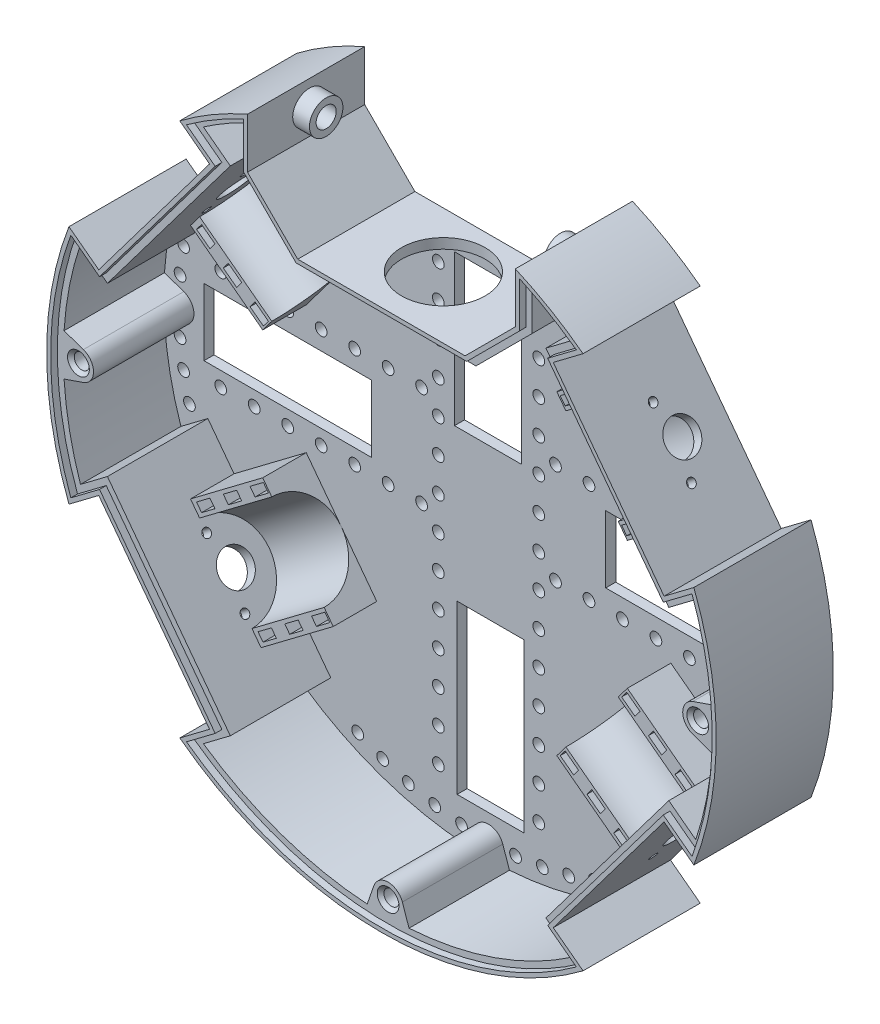
SolidWorks part; units mm, degrees
ref_plane "Front Plane" through (0, 0, 0) normal (0, 0, 1) x (1, 0, 0)
ref_plane "Top Plane" through (0, 0, 0) normal (0, 1, 0) x (1, 0, 0)
ref_plane "Right Plane" through (0, 0, 0) normal (1, 0, 0) x (0, 0, -1)
sketch "Sketch1" plane through (0, 0, 0) normal (0, 0, 1) x (1, 0, 0)
  circle A0 centre (0, 0) radius 100
  dimension "D1" = 200
extrude "Boss-Extrude1" add sketch "Sketch1" along normal blind 3
sketch "Sketch2" plane through (0, 0, 3) normal (0, 0, 1) x (1, 0, 0)
  line L0 (-40, 91.6515) -> (-40, 76.6515)
  line L1 (-40, 76.6515) -> (-25, 61.6515)
  line L2 (-25, 61.6515) -> (25, 61.6515)
  line L3 (25, 61.6515) -> (40, 76.6515)
  line L4 (40, 76.6515) -> (40, 91.6515)
  line L5 (-40, 91.6515) -> (40, 91.6515) construction
  line L6 (-40, 76.6515) -> (40, 76.6515) construction
  circle A0 centre (0, 0) radius 100 construction
  arc A1 (-40, 91.6515) -> (40, 91.6515) centre (0, 0) cw
  dimension "D1" = 80
  dimension "D2" = 15
  dimension "D3" = 15
  dimension "D4" = 15
extrude "Cut-Extrude1" cut sketch "Sketch2" against normal blind 3
sketch "Sketch3" plane through (0, 0, 3) normal (0, 0, 1) x (1, 0, 0)
  line L0 (0, 0) -> (67.884, 51.1543) construction
  line L1 (0, 0) -> (100, 0) construction
  line L2 (51.3341, 73.1168) -> (84.4339, 29.1918)
  line L3 (51.3341, 73.1168) -> (75.2932, 91.1712)
  line L4 (84.4339, 29.1918) -> (108.393, 47.2463)
  line L5 (75.2932, 91.1712) -> (108.393, 47.2463)
  arc A1 (-40, 91.6515) -> (40, 91.6515) centre (0, 0) ccw construction
  dimension "D1" = 37
  dimension "D2" = 55
  dimension "D3" = 30
  dimension "D4" = 85
extrude "Cut-Extrude2" cut sketch "Sketch3" against normal blind 3
sketch "Sketch4" plane through (0, 0, 3) normal (0, 0, 1) x (1, 0, 0)
  line L0 (57.3523, 65.1304) -> (78.4158, 37.1782)
  line L1 (57.3523, 65.1304) -> (33.3932, 47.0759)
  line L2 (78.4158, 37.1782) -> (54.4567, 19.1237)
  line L3 (33.3932, 47.0759) -> (54.4567, 19.1237)
  line L4 (51.3341, 73.1168) -> (84.4339, 29.1918) construction
  point P6 (67.884, 51.1543)
  dimension "D1" = 35
  dimension "D2" = 30
extrude "Boss-Extrude2" add sketch "Sketch4" along normal blind 13
sketch "Sketch5" plane through (67.884, 51.1543, 0) normal (0.7986, 0.6018, 0) x (0, 0, -1)
  line L0 (-16, -17.5) -> (-16, 17.5) construction
  circle A0 centre (-16, 0) radius 13
  dimension "D1" = 26
extrude "Cut-Extrude3" cut sketch "Sketch5" against normal blind 50
sketch "Sketch9" plane through (0, 0, 16) normal (0, 0, 1) x (1, 0, 0)
  line L0 (53.1159, 59.1208) -> (71.4712, 34.7624) construction
  line L1 (75.7076, 40.772) -> (60.0604, 61.5365) construction
  line L2 (67.884, 51.1543) -> (62.2936, 46.9416) construction
  line L3 (68.7224, 34.2561) -> (72.7156, 37.2652)
  line L4 (68.7224, 34.2561) -> (70.2269, 32.2595)
  line L5 (72.7156, 37.2652) -> (74.2201, 35.2686)
  line L6 (70.2269, 32.2595) -> (74.2201, 35.2686)
  line L7 (68.7224, 34.2561) -> (74.2201, 35.2686) construction
  line L8 (72.7156, 37.2652) -> (70.2269, 32.2595) construction
  line L9 (51.7485, 22.7176) -> (75.7076, 40.772) construction
  line L10 (50.3821, 58.5945) -> (54.3753, 61.6035)
  line L11 (50.3821, 58.5945) -> (51.8565, 56.638)
  line L12 (54.3753, 61.6035) -> (55.8496, 59.6471)
  line L13 (51.8565, 56.638) -> (55.8496, 59.6471)
  line L14 (50.3821, 58.5945) -> (55.8496, 59.6471) construction
  line L15 (54.3753, 61.6035) -> (51.8565, 56.638) construction
  line L16 (60.0604, 61.5365) -> (36.1014, 43.4821) construction
  dimension "D1" = 5
  dimension "D2" = 30.5
  dimension "D3" = 7
  dimension "D4" = 2.5
  dimension "D5" = 2.4498
  dimension "D6" = 5
extrude "Cut-Extrude5" cut sketch "Sketch9" against normal through all
pattern_linear "LPattern1" count 3 spacing 10 along (-0.7986, -0.6018, 0) of "Cut-Extrude5"
sketch "Sketch29" plane through (0, 0, 0) normal (0, 0, -1) x (-1, 0, 0)
  line L0 (-72.7156, 37.2652) -> (-68.7224, 34.2561)
  line L1 (-72.7156, 37.2652) -> (-55.8496, 59.6471)
  line L2 (-68.7224, 34.2561) -> (-51.8565, 56.638)
  line L3 (-55.8496, 59.6471) -> (-51.8565, 56.638)
  line L4 (-51.8565, 56.638) -> (-55.8496, 59.6471) construction
  line L17 (-64.7292, 31.2471) -> (-47.8633, 53.6289)
  line L18 (-60.736, 28.238) -> (-43.8701, 50.6198)
  line L19 (-47.8633, 53.6289) -> (-43.8701, 50.6198)
  line L20 (-56.7429, 25.2289) -> (-39.8769, 47.6108)
  line L21 (-52.7497, 22.2198) -> (-35.8838, 44.6017)
  line L22 (-39.8769, 47.6108) -> (-35.8838, 44.6017)
  line M1 (-64.7292, 31.2471) -> (-60.736, 28.238)
  line M11 (-35.8838, 44.6017) -> (-39.8769, 47.6108)
  line M13 (-56.7429, 25.2289) -> (-52.7497, 22.2198)
  line M19 (-43.8701, 50.6198) -> (-47.8633, 53.6289)
  line M25 (-72.7156, 37.2652) -> (-68.7224, 34.2561)
  line M31 (-51.8565, 56.638) -> (-55.8496, 59.6471)
  dimension "D1" = 3
extrude "Cut-Extrude15" cut sketch "Sketch29" against normal blind 2 contours L2 L1 M25 M31 | L18 L17 M1 M19 | L21 L20 M13 M11
mirror "Mirror1" about plane through (0, 0, 0) normal (1, 0, 0) of "Cut-Extrude15", "Cut-Extrude5", "LPattern1", "Cut-Extrude2", "Boss-Extrude2", "Cut-Extrude3" second plane through (0, 0, 0) second plane normal (0, 1, 0)
ref_plane "Plane1" through (-93.3343, -35.8987, 3) normal (-0.7986, -0.6018, 0) x (0, 0, 1)
sketch "Sketch13" plane through (0, 0, 3) normal (0, 0, 1) x (1, 0, 0)
  line L18 (-47.1328, -73.7072) -> (-55.1831, -79.7736)
  line L19 (55.1831, -79.7736) -> (47.1328, -73.7072)
  line L20 (47.1328, -73.7072) -> (83.8435, -24.9904)
  line L21 (83.8435, -24.9904) -> (91.8938, -31.0568)
  line L22 (91.8938, 31.0568) -> (83.8435, 24.9904)
  line L28 (83.8435, 24.9904) -> (47.1328, 73.7072)
  line L31 (47.1328, 73.7072) -> (55.1831, 79.7736)
  line L32 (43, 86.9483) -> (43, 75.4089)
  line L33 (43, 75.4089) -> (26.2426, 58.6515)
  line L51 (26.2426, 58.6515) -> (-26.2426, 58.6515)
  line L52 (-26.2426, 58.6515) -> (-43, 75.4089)
  line L53 (-43, 75.4089) -> (-43, 86.9483)
  line L54 (-55.1831, 79.7736) -> (-47.1328, 73.7072)
  line L55 (-47.1328, 73.7072) -> (-83.8435, 24.9904)
  line L56 (-83.8435, 24.9904) -> (-91.8938, 31.0568)
  line L57 (-91.8938, -31.0568) -> (-83.8435, -24.9904)
  line L58 (-83.8435, -24.9904) -> (-47.1328, -73.7072)
  line L59 (-51.3341, -73.1168) -> (-60.2344, -79.8236)
  line L65 (-84.4339, -29.1918) -> (-51.3341, -73.1168)
  line L68 (-93.3343, -35.8987) -> (-84.4339, -29.1918)
  line L69 (-84.4339, 29.1918) -> (-93.3343, 35.8987)
  line L70 (-51.3341, 73.1168) -> (-84.4339, 29.1918)
  line L71 (-60.2344, 79.8236) -> (-51.3341, 73.1168)
  line L72 (-40, 76.6515) -> (-40, 91.6515)
  line L73 (-25, 61.6515) -> (-40, 76.6515)
  line L74 (25, 61.6515) -> (-25, 61.6515)
  line L75 (40, 76.6515) -> (25, 61.6515)
  line L76 (40, 91.6515) -> (40, 76.6515)
  line L80 (51.3341, 73.1168) -> (60.2344, 79.8236)
  line L86 (84.4339, 29.1918) -> (51.3341, 73.1168)
  line L87 (93.3343, 35.8987) -> (84.4339, 29.1918)
  line L88 (84.4339, -29.1918) -> (93.3343, -35.8987)
  line L89 (51.3341, -73.1168) -> (84.4339, -29.1918)
  line L90 (60.2344, -79.8236) -> (51.3341, -73.1168)
  line L91 (-51.3341, -73.1168) -> (-60.2344, -79.8236)
  line L92 (-84.4339, -29.1918) -> (-51.3341, -73.1168)
  line L93 (-93.3343, -35.8987) -> (-84.4339, -29.1918)
  line L94 (-84.4339, 29.1918) -> (-93.3343, 35.8987)
  line L95 (-51.3341, 73.1168) -> (-84.4339, 29.1918)
  line L96 (-60.2344, 79.8236) -> (-51.3341, 73.1168)
  line L97 (-40, 76.6515) -> (-40, 91.6515)
  line L98 (-25, 61.6515) -> (-40, 76.6515)
  line L99 (25, 61.6515) -> (-25, 61.6515)
  line L100 (40, 76.6515) -> (25, 61.6515)
  line L101 (40, 91.6515) -> (40, 76.6515)
  line L102 (51.3341, 73.1168) -> (60.2344, 79.8236)
  line L103 (84.4339, 29.1918) -> (51.3341, 73.1168)
  line L104 (93.3343, 35.8987) -> (84.4339, 29.1918)
  line L105 (84.4339, -29.1918) -> (93.3343, -35.8987)
  line L106 (51.3341, -73.1168) -> (84.4339, -29.1918)
  line L107 (60.2344, -79.8236) -> (51.3341, -73.1168)
  arc A6 (-55.1831, -79.7736) -> (55.1831, -79.7736) centre (0, 0) ccw
  arc A9 (91.8938, -31.0568) -> (91.8938, 31.0568) centre (0, 0) ccw
  arc A15 (55.1831, 79.7736) -> (43, 86.9483) centre (0, 0) ccw
  arc A16 (-43, 86.9483) -> (-55.1831, 79.7736) centre (0, 0) ccw
  arc A20 (-91.8938, 31.0568) -> (-91.8938, -31.0568) centre (0, 0) ccw
  arc A21 (-60.2344, -79.8236) -> (60.2344, -79.8236) centre (0, 0) ccw
  arc A22 (-93.3343, 35.8987) -> (-93.3343, -35.8987) centre (0, 0) ccw
  arc A26 (-40, 91.6515) -> (-60.2344, 79.8236) centre (0, 0) ccw
  arc A27 (60.2344, 79.8236) -> (40, 91.6515) centre (0, 0) ccw
  arc A28 (93.3343, -35.8987) -> (93.3343, 35.8987) centre (0, 0) ccw
  arc A29 (-60.2344, -79.8236) -> (60.2344, -79.8236) centre (0, 0) ccw
  arc A30 (-93.3343, 35.8987) -> (-93.3343, -35.8987) centre (0, 0) ccw
  arc A31 (-40, 91.6515) -> (-60.2344, 79.8236) centre (0, 0) ccw
  arc A32 (60.2344, 79.8236) -> (40, 91.6515) centre (0, 0) ccw
  arc A33 (93.3343, -35.8987) -> (93.3343, 35.8987) centre (0, 0) ccw
  dimension "D1" = 0
  dimension "D2" = 3
extrude "Boss-Extrude3" add sketch "Sketch13" along normal blind 30 and the other way blind 3
sketch "Sketch14" plane through (67.884, -51.1543, 0) normal (0.7986, -0.6018, 0) x (0, 0, -1)
  line L0 (0, 0) -> (-16, 0) construction
  line L1 (-16, 9.5) -> (-16, -9.5) construction
  circle A0 centre (-16, 9.5) radius 1.25
  circle A1 centre (-16, -9.5) radius 1.25
  circle A2 centre (-13, 0) radius 5
  dimension "D2" = 2.5
  dimension "D3" = 10
  dimension "D1" = 19
  dimension "D4" = 3
  dimension "D5" = 16
extrude "Cut-Extrude6" cut sketch "Sketch14" against normal blind 6
mirror "Mirror2" about plane through (0, 0, 0) normal (1, 0, 0) of "Cut-Extrude6" second plane through (0, 0, 0) second plane normal (0, 1, 0)
sketch "Sketch15" plane through (0, 0, 3) normal (0, 0, 1) x (1, 0, 0)
  line L0 (-35, -0.6089) -> (35, 0.6089) construction
  line L1 (-85, 9.3911) -> (-35, 9.3911)
  line L2 (-85, 9.3911) -> (-85, -10.6089)
  line L3 (-85, -10.6089) -> (-35, -10.6089)
  line L4 (-35, 9.3911) -> (-35, -10.6089)
  line L5 (-85, 9.3911) -> (-35, -10.6089) construction
  line L6 (-85, -10.6089) -> (-35, 9.3911) construction
  line L7 (35, -9.3911) -> (85, -9.3911)
  line L8 (35, -9.3911) -> (35, 10.6089)
  line L9 (35, 10.6089) -> (85, 10.6089)
  line L10 (85, -9.3911) -> (85, 10.6089)
  line L11 (35, -9.3911) -> (85, 10.6089) construction
  line L12 (35, 10.6089) -> (85, -9.3911) construction
  line L13 (-9.3911, -35) -> (10.6089, -35)
  line L14 (-9.3911, -35) -> (-9.3911, -85)
  line L15 (-9.3911, -85) -> (10.6089, -85)
  line L16 (10.6089, -35) -> (10.6089, -85)
  line L17 (-9.3911, -35) -> (10.6089, -85) construction
  line L18 (-9.3911, -85) -> (10.6089, -35) construction
  line L19 (-10.174, 55) -> (9.826, 55)
  line L20 (-10.174, 55) -> (-10.174, 10)
  line L21 (-10.174, 10) -> (9.826, 10)
  line L22 (9.826, 55) -> (9.826, 10)
  line L23 (-10.174, 55) -> (9.826, 10) construction
  line L24 (-10.174, 10) -> (9.826, 55) construction
  line L25 (-35, 9.3911) -> (35, 10.6089) construction
  line L26 (35, -9.3911) -> (-35, -10.6089) construction
  line L27 (0.6089, -35) -> (0, 0) construction
  line L28 (0, 0) -> (-0.174, 10) construction
  point P0 (-60, -0.6089)
  point P5 (60, 0.6089)
  point P10 (0.6089, -60)
  point P15 (-0.174, 32.5)
  dimension "D1" = 50
  dimension "D2" = 20
  dimension "D3" = 70
  dimension "D4" = 35
  dimension "D5" = 10
  dimension "D6" = 45
  dimension "D7" = 20
extrude "Cut-Extrude7" cut sketch "Sketch15" against normal through all
sketch "Sketch19" plane through (0, 0, 3) normal (0, 0, 1) x (1, 0, 0)
  line L0 (0, 0) -> (-92.5, 0) construction
  circle A0 centre (-92.5, 0) radius 1.75
  dimension "D1" = 3.5
  dimension "D2" = 92.5
extrude "Cut-Extrude10" cut sketch "Sketch19" against normal through all
pattern_circular "CirPattern2" count 4 every 5 about axis through (0, 0, 0) along (0, 0, 1) of "Cut-Extrude10"
mirror "Mirror3" about plane through (0, 0, 0) normal (1, 0, 0) of "Cut-Extrude10", "CirPattern2"
sketch "Sketch20" plane through (0, 0, 3) normal (0, 0, 1) x (1, 0, 0)
  line L0 (0, 0) -> (0, -92.5) construction
  circle A0 centre (0, -92.5) radius 1.75
  dimension "D2" = 3.5
  dimension "D1" = 92.5
extrude "Cut-Extrude11" cut sketch "Sketch20" against normal through all
pattern_circular "CirPattern3" count 6 every 5 about axis through (0, 0, 0) along (0, 0, 1) of "Cut-Extrude11"
sketch "Sketch23" plane through (0, 0, 3) normal (0, 0, 1) x (1, 0, 0)
  line L0 (-50, 15) -> (-50, -15) construction
  line L1 (50, 15) -> (50, -15) construction
  line L2 (-50, 0) -> (50, 0) construction
  line L3 (0, 0) -> (0, -50) construction
  line L4 (-15, -50) -> (15, -50) construction
  line L5 (0, -18.15) -> (0, 18.15) construction
  circle A0 centre (-50, 15) radius 1.75
  circle A1 centre (-50, -15) radius 1.75
  circle A2 centre (50, -15) radius 1.75
  circle A3 centre (50, 15) radius 1.75
  circle A4 centre (-15, -50) radius 1.75
  circle A5 centre (15, -50) radius 1.75
  circle A6 centre (-60, 15) radius 1.75
  circle A7 centre (-60, -15) radius 1.75
  circle A8 centre (-70, 15) radius 1.75
  circle A9 centre (-70, -15) radius 1.75
  circle A10 centre (-80, 15) radius 1.75
  circle A11 centre (-80, -15) radius 1.75
  circle A12 centre (80, -15) radius 1.75
  circle A13 centre (80, 15) radius 1.75
  circle A14 centre (70, -15) radius 1.75
  circle A15 centre (70, 15) radius 1.75
  circle A16 centre (60, -15) radius 1.75
  circle A17 centre (60, 15) radius 1.75
  circle A18 centre (-15, -40) radius 1.75
  circle A19 centre (15, -40) radius 1.75
  circle A20 centre (-15, -30) radius 1.75
  circle A21 centre (15, -30) radius 1.75
  circle A22 centre (-15, -20) radius 1.75
  circle A23 centre (15, -20) radius 1.75
  circle A24 centre (-15, -10) radius 1.75
  circle A25 centre (15, -10) radius 1.75
  circle A26 centre (-15, 0) radius 1.75
  circle A27 centre (15, 0) radius 1.75
  circle A28 centre (-15, 10) radius 1.75
  circle A29 centre (15, 10) radius 1.75
  circle A30 centre (-15, 20) radius 1.75
  circle A31 centre (15, 20) radius 1.75
  circle A32 centre (-15, 30) radius 1.75
  circle A33 centre (15, 30) radius 1.75
  circle A34 centre (-15, 40) radius 1.75
  circle A35 centre (15, 40) radius 1.75
  circle A36 centre (-15, 50) radius 1.75
  circle A37 centre (15, 50) radius 1.75
  circle A38 centre (-15, -60) radius 1.75
  circle A39 centre (15, -60) radius 1.75
  circle A40 centre (-15, -70) radius 1.75
  circle A41 centre (15, -70) radius 1.75
  circle A42 centre (-15, -80) radius 1.75
  circle A43 centre (15, -80) radius 1.75
  circle A44 centre (-40, 15) radius 1.75
  circle A45 centre (-40, -15) radius 1.75
  circle A46 centre (-30, 15) radius 1.75
  circle A47 centre (-30, -15) radius 1.75
  circle A48 centre (-20, 15) radius 1.75
  circle A49 centre (-20, -15) radius 1.75
  circle A50 centre (40, 15) radius 1.75
  circle A51 centre (40, -15) radius 1.75
  circle A52 centre (30, 15) radius 1.75
  circle A53 centre (30, -15) radius 1.75
  circle A54 centre (20, 15) radius 1.75
  circle A55 centre (20, -15) radius 1.75
  dimension "D3" = 3.5
  dimension "D1" = 100
  dimension "D2" = 30
  dimension "D4" = 50
  dimension "D5" = 4
  dimension "D6" = 11
  dimension "D7" = 4
  dimension "D8" = 4
  dimension "D9" = 4
extrude "Cut-Extrude12" cut sketch "Sketch23" against normal through all
sketch "Sketch25" plane through (40, 0, 0) normal (-1, 0, 0) x (0, 0, 1)
  line L0 (16.5, 76.6515) -> (16.5, 91.6515) construction
  line L1 (0, 76.6515) -> (33, 76.6515) construction
  line L3 (0, 84.1515) -> (33, 84.1515) construction
  line L4 (0, 76.6515) -> (0, 91.6515) construction
  line L6 (0, 91.6515) -> (33, 91.6515) construction
  circle A0 centre (16.5, 84.1515) radius 5
  dimension "D1" = 10
extrude "Boss-Extrude5" add sketch "Sketch25" along normal blind 5
sketch "Sketch26" plane through (35, 0, 0) normal (-1, 0, 0) x (0, 0, 1)
  line L0 (16.5, 89.1515) -> (16.5, 79.1515) construction
  line L1 (11.5, 84.1515) -> (21.5, 84.1515) construction
  circle A0 centre (16.5, 84.1515) radius 5 construction
  circle A1 centre (16.5, 84.1515) radius 3
  dimension "D1" = 6
extrude "Cut-Extrude13" cut sketch "Sketch26" against normal blind 8
mirror "Mirror4" about plane through (0, 0, 0) normal (1, 0, 0) of "Boss-Extrude5", "Cut-Extrude13"
sketch "Sketch28" plane through (0, 61.6515, 0) normal (0, -1, 0) x (1, 0, 0)
  line L0 (0, 33) -> (0, 0) construction
  line L3 (25, 33) -> (-25, 33) construction
  circle A0 centre (0, 16.5) radius 12.5
  dimension "D1" = 25
extrude "Cut-Extrude14" cut sketch "Sketch28" against normal blind 30 and the other way blind 15
sketch "Sketch30" plane through (0, 0, 3) normal (0, 0, 1) x (1, 0, 0)
  line L0 (-91.0279, 4.2524) -> (-96.7984, 6.25)
  line L1 (-91.0279, -4.2524) -> (-96.7984, -6.25)
  line L2 (-96.7984, 6.25) -> (-96.7984, -6.25) construction
  line L3 (-96.7984, 0) -> (-92.5, 0) construction
  arc A0 (-91.0279, -4.2524) -> (-91.0279, 4.2524) centre (-92.5, 0) ccw
  circle A5 centre (-92.5, 0) radius 2.25
  arc A6 (-91.8938, 31.0568) -> (-91.8938, -31.0568) centre (0, 0) ccw construction
  arc A7 (-96.7984, 6.25) -> (-96.7984, -6.25) centre (0, 0) ccw
  dimension "D1" = 9
  dimension "D2" = 12.5
  dimension "D3" = 4.5
extrude "Boss-Extrude6" add sketch "Sketch30" along normal up to surface (30 mm away) up to face at (0, 20.0419, 33)
chamfer "Chamfer2" distance 1 angle 45 1 edges at (-90.25, 0, 33)
pattern_circular "CirPattern4" count 3 every 90 about axis through (0, 0, 0) along (0, 0, 1) of "Chamfer2", "Boss-Extrude6"
sketch "Sketch31" plane through (0, 0, 33) normal (0, 0, 1) x (1, 0, 0)
  line L20 (58.2306, -79.8162) -> (49.6536, -73.3529)
  line L23 (49.6536, -73.3529) -> (84.1977, -27.5113)
  line L28 (84.1977, -27.5113) -> (92.7748, -33.9746)
  line L31 (92.7748, 33.9746) -> (84.1977, 27.5113)
  line L51 (84.1977, 27.5113) -> (49.6536, 73.3529)
  line L52 (49.6536, 73.3529) -> (58.2306, 79.8162)
  line L53 (41.2, 89.7998) -> (41.2, 76.1545)
  line L54 (41.2, 76.1545) -> (25.4971, 60.4515)
  line L55 (25.4971, 60.4515) -> (-25.4971, 60.4515)
  line L56 (-25.4971, 60.4515) -> (-41.2, 76.1545)
  line L57 (-41.2, 76.1545) -> (-41.2, 89.7998)
  line L58 (-58.2306, 79.8162) -> (-49.6536, 73.3529)
  line L59 (-49.6536, 73.3529) -> (-84.1977, 27.5113)
  line L60 (-84.1977, 27.5113) -> (-92.7748, 33.9746)
  line L61 (-92.7748, -33.9746) -> (-84.1977, -27.5113)
  line L62 (-84.1977, -27.5113) -> (-49.6536, -73.3529)
  line L63 (-49.6536, -73.3529) -> (-58.2306, -79.8162)
  line L64 (60.2344, -79.8236) -> (51.3341, -73.1168)
  line L65 (51.3341, -73.1168) -> (84.4339, -29.1918)
  line L66 (84.4339, -29.1918) -> (93.3343, -35.8987)
  line L67 (93.3343, 35.8987) -> (84.4339, 29.1918)
  line L68 (84.4339, 29.1918) -> (51.3341, 73.1168)
  line L69 (51.3341, 73.1168) -> (60.2344, 79.8236)
  line L70 (40, 91.6515) -> (40, 76.6515)
  line L71 (40, 76.6515) -> (25, 61.6515)
  line L72 (25, 61.6515) -> (-25, 61.6515)
  line L73 (-25, 61.6515) -> (-40, 76.6515)
  line L74 (-40, 76.6515) -> (-40, 91.6515)
  line L75 (-60.2344, 79.8236) -> (-51.3341, 73.1168)
  line L76 (-51.3341, 73.1168) -> (-84.4339, 29.1918)
  line L77 (-84.4339, 29.1918) -> (-93.3343, 35.8987)
  line L78 (-93.3343, -35.8987) -> (-84.4339, -29.1918)
  line L79 (-84.4339, -29.1918) -> (-51.3341, -73.1168)
  line L80 (-51.3341, -73.1168) -> (-60.2344, -79.8236)
  line L81 (60.2344, -79.8236) -> (51.3341, -73.1168)
  line L82 (51.3341, -73.1168) -> (84.4339, -29.1918)
  line L83 (84.4339, -29.1918) -> (93.3343, -35.8987)
  line L84 (93.3343, 35.8987) -> (84.4339, 29.1918)
  line L85 (84.4339, 29.1918) -> (51.3341, 73.1168)
  line L86 (51.3341, 73.1168) -> (60.2344, 79.8236)
  line L87 (40, 91.6515) -> (40, 76.6515)
  line L88 (40, 76.6515) -> (25, 61.6515)
  line L89 (25, 61.6515) -> (-25, 61.6515)
  line L90 (-25, 61.6515) -> (-40, 76.6515)
  line L91 (-40, 76.6515) -> (-40, 91.6515)
  line L92 (-60.2344, 79.8236) -> (-51.3341, 73.1168)
  line L93 (-51.3341, 73.1168) -> (-84.4339, 29.1918)
  line L94 (-84.4339, 29.1918) -> (-93.3343, 35.8987)
  line L95 (-93.3343, -35.8987) -> (-84.4339, -29.1918)
  line L96 (-84.4339, -29.1918) -> (-51.3341, -73.1168)
  line L97 (-51.3341, -73.1168) -> (-60.2344, -79.8236)
  arc A15 (92.7748, -33.9746) -> (92.7748, 33.9746) centre (0, 0) ccw
  arc A16 (58.2306, 79.8162) -> (41.2, 89.7998) centre (0, 0) ccw
  arc A17 (-41.2, 89.7998) -> (-58.2306, 79.8162) centre (0, 0) ccw
  arc A18 (-92.7748, 33.9746) -> (-92.7748, -33.9746) centre (0, 0) ccw
  arc A19 (-58.2306, -79.8162) -> (58.2306, -79.8162) centre (0, 0) ccw
  arc A20 (-60.2344, -79.8236) -> (60.2344, -79.8236) centre (0, 0) ccw
  arc A21 (93.3343, -35.8987) -> (93.3343, 35.8987) centre (0, 0) ccw
  arc A22 (60.2344, 79.8236) -> (40, 91.6515) centre (0, 0) ccw
  arc A23 (-40, 91.6515) -> (-60.2344, 79.8236) centre (0, 0) ccw
  arc A24 (-93.3343, 35.8987) -> (-93.3343, -35.8987) centre (0, 0) ccw
  arc A25 (-60.2344, -79.8236) -> (60.2344, -79.8236) centre (0, 0) ccw
  arc A26 (93.3343, -35.8987) -> (93.3343, 35.8987) centre (0, 0) ccw
  arc A27 (60.2344, 79.8236) -> (40, 91.6515) centre (0, 0) ccw
  arc A28 (-40, 91.6515) -> (-60.2344, 79.8236) centre (0, 0) ccw
  arc A29 (-93.3343, 35.8987) -> (-93.3343, -35.8987) centre (0, 0) ccw
  dimension "D1" = 0
  dimension "D2" = 1.2
extrude "Boss-Extrude7" add sketch "Sketch31" along normal blind 2
chamfer "Chamfer3" distance 4 angle 45 24 edges at (62.7326, 29.7425, 2) (45.8667, 52.1244, 2) (54.7463, 23.7244, 2) (37.8803, 46.1062, 2) (70.719, 35.7607, 2) (53.8531, 58.1425, 2) (62.7326, -29.7425, 2) (45.8667, -52.1244, 2) (54.7463, -23.7244, 2) (37.8803, -46.1062, 2) (70.719, -35.7607, 2) (53.8531, -58.1425, 2) (-62.7326, 29.7425, 2) (-45.8667, 52.1244, 2) (-54.7463, 23.7244, 2) (-37.8803, 46.1062, 2) (-70.719, 35.7607, 2) (-53.8531, 58.1425, 2) (-62.7326, -29.7425, 2) (-45.8667, -52.1244, 2) (-54.7463, -23.7244, 2) (-37.8803, -46.1062, 2) (-70.719, -35.7607, 2) (-53.8531, -58.1425, 2)
